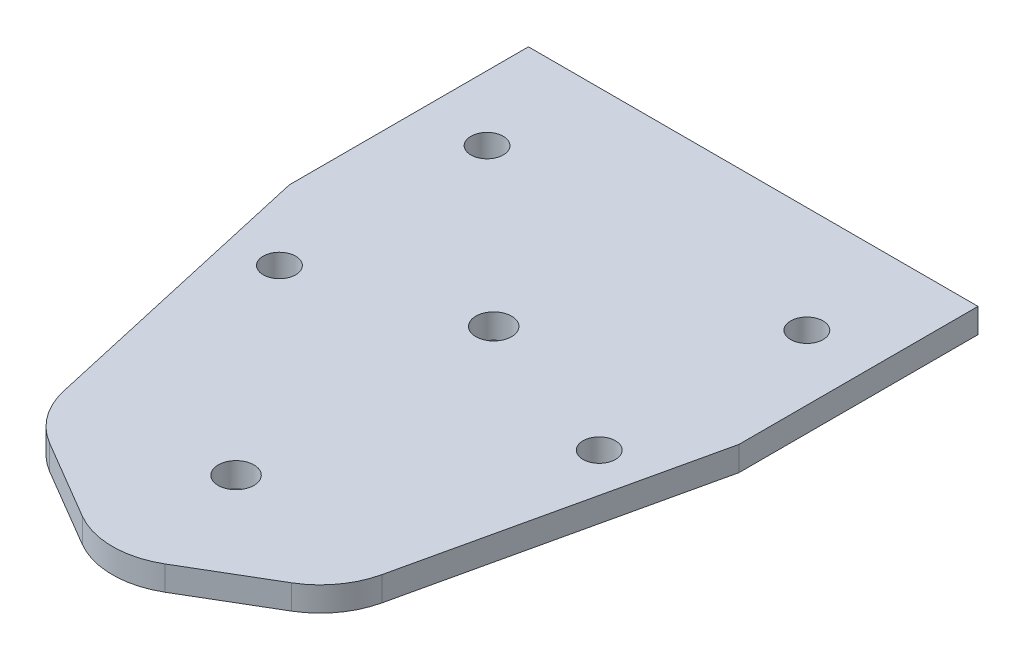
SolidWorks part; units mm, degrees
ref_plane "Front Plane" through (0, 0, 0) normal (0, 0, 1) x (1, 0, 0)
ref_plane "Top Plane" through (0, 0, 0) normal (0, 1, 0) x (1, 0, 0)
ref_plane "Right Plane" through (0, 0, 0) normal (1, 0, 0) x (0, 0, -1)
sketch "Sketch1" plane through (0, 0, 0) normal (0, 1, 0) x (1, 0, 0)
  line L1 (-27.5, -40) -> (27.5, -40)
  line L2 (-27.5, -40) -> (-27.5, 40)
  line L3 (-27.5, 40) -> (27.5, 40)
  line L4 (27.5, -40) -> (27.5, 40)
  line L5 (-27.5, -40) -> (27.5, 40) construction
  line L6 (-27.5, 40) -> (27.5, -40) construction
  point P0 (0, 0)
  dimension "D1" = 55
  dimension "D2" = 80
extrude "Boss-Extrude1" add sketch "Sketch1" along normal blind 3
sketch "Sketch2" plane through (0, 3, 0) normal (0, 1, 0) x (1, 0, 0)
  line L0 (0, 40) -> (0, -40) construction
  line L1 (27.5, 40) -> (-27.5, 40) construction
  line L2 (-27.5, -40) -> (27.5, -40) construction
  line L3 (27.5, 40) -> (-27.5, 40) construction
  line L4 (-27.5, 40) -> (-27.5, -40) construction
  circle A0 centre (0, 8.25) radius 2.185
  circle A1 centre (0, -23.271) radius 2.185
  circle A2 centre (-19.5625, 27) radius 1.9844
  circle A3 centre (-19.5625, 1.6) radius 1.9844
  circle A4 centre (19.5625, 27) radius 1.9844
  circle A5 centre (19.5625, 1.6) radius 1.9844
  dimension "D1" = 4.37
  dimension "D2" = 31.521
  dimension "D3" = 31.75
  dimension "D4" = 25.4
  dimension "D5" = 3.9688
  dimension "D6" = 7.9375
  dimension "D7" = 13
extrude "Cut-Extrude1" cut sketch "Sketch2" against normal through all
sketch "Sketch3" plane through (0, 3, 0) normal (0, 1, 0) x (1, 0, 0)
  line L0 (0, -40) -> (27.5, -40)
  line L1 (-27.5, -40) -> (27.5, -40) construction
  line L5 (27.5, -40) -> (27.5, 10.7529)
  line L6 (27.5, -40) -> (27.5, 40) construction
  line L7 (27.5, 10.7529) -> (18.5103, -29.0945)
  line L8 (18.5103, -29.0945) -> (0, -40)
  line M7 (27.5, -40) -> (27.5, 40)
  line M12 (-27.5, -40) -> (27.5, -40)
extrude "Cut-Extrude2" cut sketch "Sketch3" against normal through all contours L7 L8 M12 M7 region at (20.8678, 3, 26.157)
mirror "Mirror1" about plane through (0, 0, 0) normal (1, 0, 0) of "Cut-Extrude2"
fillet "Fillet1" radius 10 3 edges at (18.5103, 1.5, 29.0945) (0, 1.5, 40) (-18.5103, 1.5, 29.0945)
equation "\"pulley_pitch_diam\"= 12.73mm"
equation "\"pulley_total_width\"= 16mm"
equation "\"pulley_total_diam\"= 16mm"
equation "\"belt_width\"= 6mm"
equation "\"material_thickness\"= 3mm"
equation "\"shaft_diam\"= 8mm"
equation "\"bearing_od\"= 22mm"
equation "\"bearing_thickness\"= 7mm"
equation "\"D1@Boss-Extrude1\"=\"material_thickness\""
